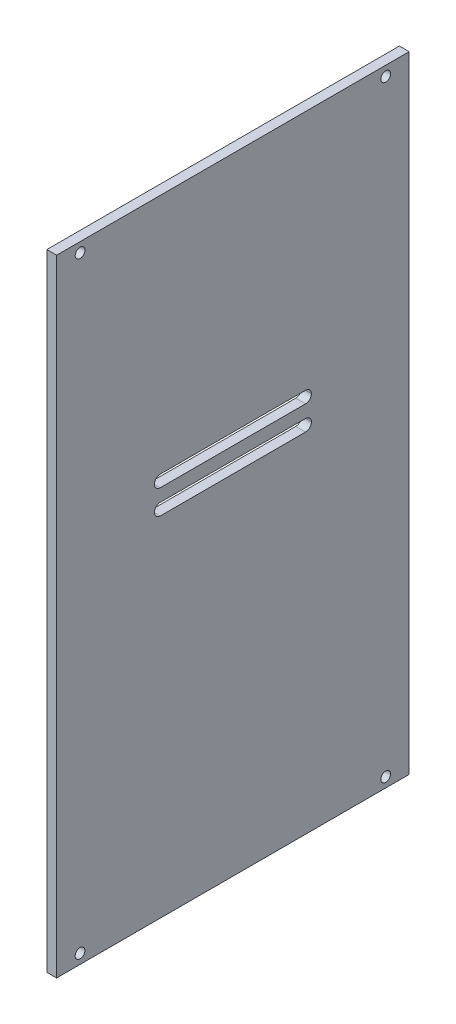
SolidWorks part; units mm, degrees
ref_plane "Front Plane" through (0, 0, 0) normal (0, 0, 1) x (1, 0, 0)
ref_plane "Top Plane" through (0, 0, 0) normal (0, 1, 0) x (1, 0, 0)
ref_plane "Right Plane" through (0, 0, 0) normal (1, 0, 0) x (0, 0, -1)
sketch "Sketch1" plane through (0, 0, 0) normal (1, 0, 0) x (0, 0, -1)
  line L0 (0, 160.065) -> (0, -160.065) construction
  line L1 (-90.15, 160.065) -> (-90.15, -160.065)
  line L2 (-90.15, -160.065) -> (90.15, -160.065)
  line L3 (90.15, -160.065) -> (90.15, 160.065)
  line L4 (90.15, 160.065) -> (-90.15, 160.065)
  line L5 (-90.15, 0) -> (90.15, 0) construction
  circle A0 centre (-78.15, 155.065) radius 2.5
  circle A1 centre (78.15, 155.065) radius 2.5
  circle A2 centre (-78.15, -155.065) radius 2.5
  circle A3 centre (78.15, -155.065) radius 2.5
  dimension "D3" = 5
  dimension "D4" = 5
  dimension "D5" = 12
  dimension "D6" = 5
  dimension "D7" = 5
  dimension "D8" = 12
  dimension "D9" = 5
  dimension "D10" = 12
  dimension "D11" = 5
  dimension "D12" = 5
  dimension "D13" = 12
  dimension "D14" = 5
  dimension "D1" = 320.13
  dimension "D2" = 180.3
extrude "Boss-Extrude1" add sketch "Sketch1" along normal blind 5
sketch "Sketch2" plane through (5, 0, 0) normal (1, 0, 0) x (0, 0, -1)
  line L0 (-90.15, 33.575) -> (90.15, 33.575) construction
  line L1 (-90.15, 160.065) -> (-90.15, -160.065) construction
  line L2 (90.15, -160.065) -> (90.15, 160.065) construction
  line L3 (90.15, 160.065) -> (-90.15, 160.065) construction
  line L4 (-90.15, 27.325) -> (90.15, 27.325) construction
  line L5 (40.15, 30.575) -> (-40.15, 30.575)
  line L6 (40.15, 30.575) -> (40.15, 36.575)
  line L7 (40.15, 36.575) -> (-40.15, 36.575)
  line L8 (-40.15, 30.575) -> (-40.15, 36.575)
  line L9 (40.15, 30.575) -> (-40.15, 36.575) construction
  line L10 (40.15, 36.575) -> (-40.15, 30.575) construction
  line L11 (40.15, 24.075) -> (-40.15, 24.075)
  line L12 (-40.15, 24.075) -> (-40.15, 18.075)
  line L13 (40.15, 18.075) -> (-40.15, 18.075)
  line L14 (40.15, 24.075) -> (40.15, 18.075)
  point P8 (0, 33.575)
  dimension "D1" = 126.49
  dimension "D2" = 50
  dimension "D3" = 6
  dimension "D4" = 6.25
extrude "Cut-Extrude1" cut sketch "Sketch2" against normal up to next
fillet "Fillet1" radius 3 4 edges at (2.5, 36.575, -40.15) (2.5, 30.575, -40.15) (2.5, 30.575, 40.15) (2.5, 36.575, 40.15)
fillet "Fillet2" radius 3 4 edges at (2.5, 18.075, -40.15) (2.5, 24.075, -40.15) (2.5, 18.075, 40.15) (2.5, 24.075, 40.15)
